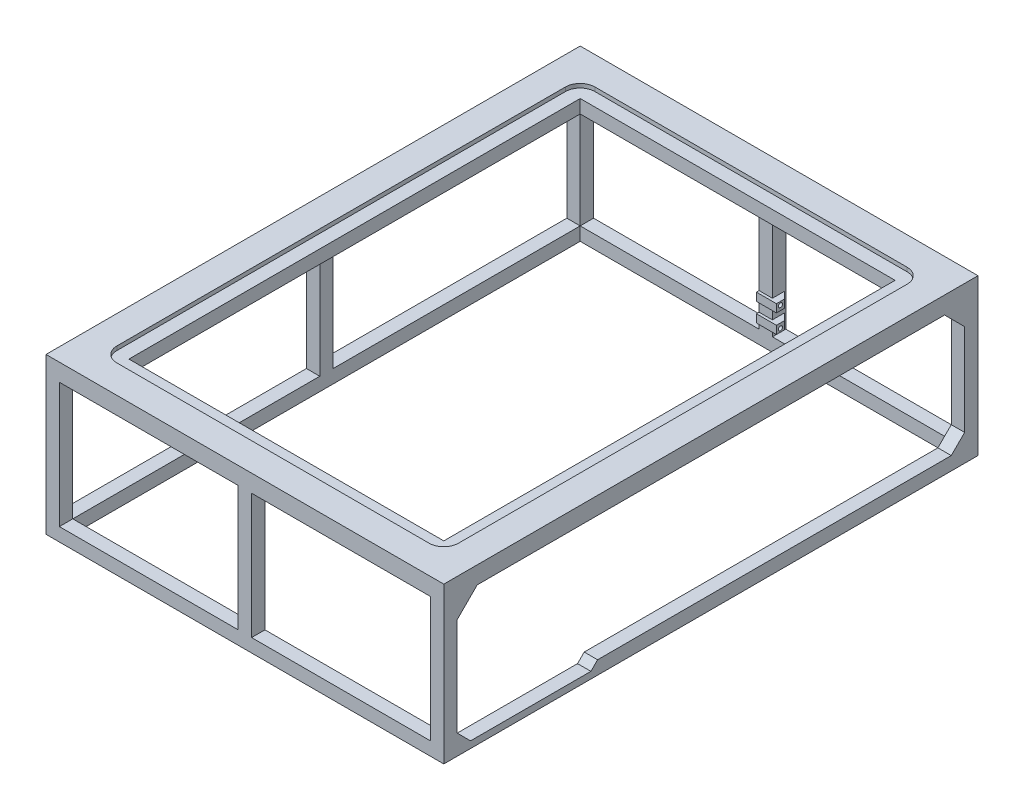
SolidWorks part; units mm, degrees
ref_plane "Front Plane" through (0, 0, 0) normal (0, 0, 1) x (1, 0, 0)
ref_plane "Top Plane" through (0, 0, 0) normal (0, 1, 0) x (1, 0, 0)
ref_plane "Right Plane" through (0, 0, 0) normal (1, 0, 0) x (0, 0, -1)
sketch "Sketch1" plane through (0, 0, 0) normal (0, 1, 0) x (1, 0, 0)
  line L1 (0, 0) -> (253.5, 0)
  line L2 (0, 0) -> (0, 355.5)
  line L3 (0, 355.5) -> (253.5, 355.5)
  line L4 (253.5, 0) -> (253.5, 355.5)
  line L5 (-22, 377.5) -> (275.5, 377.5)
  line L6 (-22, 377.5) -> (-22, -22)
  line L7 (-22, -22) -> (275.5, -22)
  line L8 (275.5, 377.5) -> (275.5, -22)
  line L9 (-12, 367.5) -> (265.5, 367.5)
  line L10 (-12, 367.5) -> (-12, -12)
  line L11 (-12, -12) -> (265.5, -12)
  line L12 (265.5, 367.5) -> (265.5, -12)
  dimension "D1" = 253.5
  dimension "D2" = 355.5
  dimension "D3" = 22
  dimension "D4" = 22
  dimension "D5" = 22
  dimension "D6" = 22
  dimension "D7" = 10
  dimension "D8" = 10
  dimension "D9" = 10
  dimension "D10" = 10
extrude "Boss-Extrude1" add sketch "Sketch1" along normal blind 10 contours L8 L5 L6 L7 L9 L12 L11 L10 region at (126.75, 0, -372.519)
sketch "Sketch2" plane through (0, 10, 0) normal (0, 1, 0) x (1, 0, 0)
  line L0 (-22, -22) -> (275.5, -22) construction
  line L1 (131.75, -22) -> (121.75, -22)
  line L2 (131.75, -22) -> (131.75, -12)
  line L3 (131.75, -12) -> (121.75, -12)
  line L4 (121.75, -22) -> (121.75, -12)
  line L5 (-12, -12) -> (265.5, -12) construction
  line L6 (-12, 367.5) -> (265.5, 367.5) construction
  line L7 (275.5, -22) -> (265.5, -22)
  line L8 (275.5, -22) -> (275.5, -12)
  line L9 (275.5, -12) -> (265.5, -12)
  line L10 (265.5, -22) -> (265.5, -12)
  line L11 (-22, -22) -> (-12, -22)
  line L12 (-22, -22) -> (-22, -12)
  line L13 (-22, -12) -> (-12, -12)
  line L14 (-12, -22) -> (-12, -12)
  line L15 (-22, 377.5) -> (-12, 377.5)
  line L16 (-22, 377.5) -> (-22, 367.5)
  line L17 (-22, 367.5) -> (-12, 367.5)
  line L18 (-12, 377.5) -> (-12, 367.5)
  line L19 (275.5, 377.5) -> (265.5, 377.5)
  line L20 (275.5, 377.5) -> (275.5, 367.5)
  line L21 (275.5, 367.5) -> (265.5, 367.5)
  line L22 (265.5, 377.5) -> (265.5, 367.5)
  line L23 (131.75, 367.5) -> (121.75, 367.5)
  line L24 (131.75, 367.5) -> (131.75, 377.5)
  line L25 (131.75, 377.5) -> (121.75, 377.5)
  line L26 (121.75, 367.5) -> (121.75, 377.5)
  line L27 (-22, 377.5) -> (275.5, 377.5) construction
  line L28 (275.5, 377.5) -> (275.5, -22) construction
  line L29 (275.5, 172.75) -> (265.5, 172.75)
  line L30 (275.5, 172.75) -> (275.5, 182.75)
  line L31 (275.5, 182.75) -> (265.5, 182.75)
  line L32 (265.5, 172.75) -> (265.5, 182.75)
  line L33 (265.5, 367.5) -> (265.5, -12) construction
  line L34 (-12, 367.5) -> (-12, -12) construction
  line L35 (-12, 172.75) -> (-22, 172.75)
  line L36 (-12, 172.75) -> (-12, 182.75)
  line L37 (-12, 182.75) -> (-22, 182.75)
  line L38 (-22, 172.75) -> (-22, 182.75)
  line L39 (-22, 377.5) -> (-22, -22) construction
  dimension "D1" = 133.75
  dimension "D2" = 10
  dimension "D3" = 133.75
  dimension "D4" = 10
  dimension "D5" = 133.75
  dimension "D6" = 10
  dimension "D7" = 184.75
  dimension "D8" = 184.75
  dimension "D9" = 10
  dimension "D10" = 184.75
extrude "Boss-Extrude2" add sketch "Sketch2" along normal blind 93.5
sketch "Sketch3" plane through (0, 103.5, 0) normal (0, 1, 0) x (1, 0, 0)
  line L1 (-22, 377.5) -> (275.5, 377.5)
  line L2 (-22, 377.5) -> (-22, -22)
  line L3 (-22, -22) -> (275.5, -22)
  line L4 (275.5, 377.5) -> (275.5, -22)
  line L9 (244.5, 346.5) -> (9, 346.5)
  line L10 (244.5, 346.5) -> (244.5, 9)
  line L11 (244.5, 9) -> (9, 9)
  line L12 (9, 346.5) -> (9, 9)
  dimension "D1" = 235.5
  dimension "D2" = 337.5
  dimension "D3" = 31
  dimension "D4" = 31
  dimension "D5" = 31
  dimension "D6" = 31
extrude "Boss-Extrude3" add sketch "Sketch3" along normal blind 10
sketch "Sketch4" plane through (0, 0, 0) normal (0, -1, 0) x (1, 0, 0)
  line L0 (-22, -177.75) -> (275.5, -177.75)
  line L1 (-22, -377.5) -> (-22, 22) construction
  line L2 (275.5, -377.5) -> (275.5, 22) construction
  line L3 (126.75, -377.5) -> (126.75, 22)
  line L4 (-22, -377.5) -> (275.5, -377.5) construction
  line L5 (-22, 22) -> (275.5, 22) construction
  line L6 (-17, -377.5) -> (-17, 22)
  line L7 (-22, -377.5) -> (275.5, -377.5)
  line L8 (-22, -377.5) -> (-22, -367.5)
  line L9 (-22, -367.5) -> (275.5, -367.5)
  line L10 (275.5, -377.5) -> (275.5, -367.5)
  line L11 (-22, 22) -> (275.5, 22)
  line L12 (-22, 22) -> (-22, 12)
  line L13 (-22, 12) -> (275.5, 12)
  line L14 (275.5, 22) -> (275.5, 12)
  line L15 (275.5, -377.5) -> (265.5, -377.5)
  line L16 (275.5, -377.5) -> (275.5, 22)
  line L17 (275.5, 22) -> (265.5, 22)
  line L18 (265.5, -377.5) -> (265.5, 22)
  line L19 (-22, -377.5) -> (-12, -377.5)
  line L20 (-22, -377.5) -> (-22, 22)
  line L21 (-22, 22) -> (-12, 22)
  line L22 (-12, -377.5) -> (-12, 22)
  line L23 (-22, 17) -> (275.5, 17)
  line L24 (-22, -372.5) -> (275.5, -372.5)
  line L25 (265.5, -367.5) -> (275.5, -377.5)
  line L26 (265.5, 12) -> (275.5, 22)
  line L27 (-22, -377.5) -> (-12, -367.5)
  line L28 (-12, 12) -> (-22, 22)
  circle A0 centre (270.5, 17) radius 1.6
  circle A1 centre (270.5, -177.75) radius 1.6
  circle A2 centre (270.5, -372.5) radius 1.6
  circle A3 centre (126.75, -372.5) radius 1.6
  circle A4 centre (-17, -372.5) radius 1.6
  circle A5 centre (-17, -177.75) radius 1.6
  circle A6 centre (-17, 17) radius 1.6
  circle A7 centre (126.75, 17) radius 1.6
  dimension "D1" = 3.2
  dimension "D2" = 3.2
  dimension "D3" = 3.2
  dimension "D4" = 3.2
  dimension "D5" = 3.2
  dimension "D6" = 3.2
  dimension "D7" = 3.2
  dimension "D8" = 3.2
extrude "Cut-Extrude1" cut sketch "Sketch4" against normal blind 1.2 contours L26 A0 L23 | L26 A0 L23 | L23 A0 L26 | L23 A0 L26 | L0 A1 | L0 A1 | L24 A2 L25 | L25 A2 L24 | L25 A2 L24 | L24 A2 L25 | L23 A7 L3 | L3 A7 L23 | L3 A7 L23 | L23 A7 L3 | L24 A3 L3 | L3 A3 L24 | L24 A3 L3 | L3 A3 L24 | L23 A6 L6 | L6 A6 L28 | L28 A6 L23 | L23 A6 L6 | L28 A6 L23 | L6 A6 L28 | L0 A5 L6 | L6 A5 L0 | L0 A5 L6 | L6 A5 L0 | L24 A4 L27 | L27 A4 L6 | L6 A4 L24 | L24 A4 L27 | L27 A4 L6 | L6 A4 L24 region at (270.5, 0, -178.4291) region at (270.5, 0, -177.0709) region at (270.8201, 0, -371.7272) region at (269.5397, 0, -372.1022) region at (271.4603, 0, -372.8978) region at (269.5397, 0, 16.6022) region at (270.8201, 0, 16.2272) region at (271.4603, 0, 17.3978) region at (127.4291, 0, -371.8209) region at (126.0709, 0, -371.8209) region at (127.4291, 0, -373.1791) region at (270.1799, 0, -373.2728) region at (126.0709, 0, 16.3209) region at (127.4291, 0, 16.3209) region at (127.4291, 0, 17.6791) region at (270.1799, 0, 17.7728) region at (-16.3209, 0, -178.4291) region at (-16.3209, 0, -177.0709) region at (126.0709, 0, -373.1791) region at (-16.0397, 0, -372.1022) region at (-16.6022, 0, -371.5397) region at (126.0709, 0, 17.6791) region at (-16.6022, 0, 16.0397) region at (-16.0397, 0, 16.6022) region at (-17.6791, 0, -178.4291) region at (-17.6791, 0, -177.0709) region at (-17.6791, 0, -371.8209) region at (-16.3209, 0, -373.1791) region at (-17.9603, 0, -372.8978) region at (-17.3978, 0, -373.4603) region at (-17.6791, 0, 16.3209) region at (-16.3209, 0, 17.6791) region at (-17.3978, 0, 17.9603) region at (-17.9603, 0, 17.3978)
sketch "Sketch6" plane through (0, 113.5, 0) normal (0, 1, 0) x (1, 0, 0)
  line L0 (253.5, 10) -> (253.5, 345.5) construction
  line L1 (10, 0) -> (243.5, 0) construction
  line L2 (0, 345.5) -> (0, 10) construction
  line L3 (243.5, 355.5) -> (10, 355.5) construction
  line L4 (253.5, 10) -> (253.5, 345.5)
  line L5 (10, 0) -> (243.5, 0)
  line L6 (0, 345.5) -> (0, 10)
  line L7 (243.5, 355.5) -> (10, 355.5)
  line L8 (254.5, 10) -> (254.5, 345.5)
  line L9 (243.5, 356.5) -> (10, 356.5)
  line L10 (-1, 345.5) -> (-1, 10)
  line L11 (10, -1) -> (243.5, -1)
  line L13 (275.5, 377.5) -> (-22, 377.5)
  line L14 (275.5, 377.5) -> (275.5, -22)
  line L15 (275.5, -22) -> (-22, -22)
  line L16 (-22, 377.5) -> (-22, -22)
  circle A0 centre (247.5, 349.5) radius 1.6 construction
  circle A1 centre (247.5, 263.625) radius 1.6 construction
  circle A2 centre (247.5, 177.75) radius 1.6 construction
  circle A3 centre (247.5, 91.875) radius 1.6 construction
  circle A4 centre (247.5, 6) radius 1.6 construction
  circle A5 centre (167, 6) radius 1.6 construction
  circle A6 centre (86.5, 6) radius 1.6 construction
  circle A7 centre (6, 6) radius 1.6 construction
  circle A8 centre (6, 91.875) radius 1.6 construction
  circle A9 centre (6, 177.75) radius 1.6 construction
  circle A10 centre (6, 263.625) radius 1.6 construction
  circle A11 centre (6, 349.5) radius 1.6 construction
  circle A12 centre (167, 349.5) radius 1.6 construction
  circle A13 centre (86.5, 349.5) radius 1.6 construction
  circle A14 centre (247.5, 349.5) radius 1.6
  circle A15 centre (247.5, 263.625) radius 1.6
  circle A16 centre (247.5, 177.75) radius 1.6
  circle A17 centre (247.5, 91.875) radius 1.6
  circle A18 centre (247.5, 6) radius 1.6
  circle A19 centre (167, 6) radius 1.6
  circle A20 centre (86.5, 6) radius 1.6
  circle A21 centre (6, 6) radius 1.6
  circle A22 centre (6, 91.875) radius 1.6
  circle A23 centre (6, 177.75) radius 1.6
  circle A24 centre (6, 263.625) radius 1.6
  circle A25 centre (6, 349.5) radius 1.6
  circle A26 centre (167, 349.5) radius 1.6
  circle A27 centre (86.5, 349.5) radius 1.6
  arc A28 (253.5, 345.5) -> (243.5, 355.5) centre (243.5, 345.5) ccw construction
  arc A29 (243.5, 0) -> (253.5, 10) centre (243.5, 10) ccw construction
  arc A30 (0, 10) -> (10, 0) centre (10, 10) ccw construction
  arc A31 (10, 355.5) -> (0, 345.5) centre (10, 345.5) ccw construction
  arc A32 (253.5, 345.5) -> (243.5, 355.5) centre (243.5, 345.5) ccw
  arc A33 (243.5, 0) -> (253.5, 10) centre (243.5, 10) ccw
  arc A34 (0, 10) -> (10, 0) centre (10, 10) ccw
  arc A35 (10, 355.5) -> (0, 345.5) centre (10, 345.5) ccw
  arc A36 (254.5, 345.5) -> (243.5, 356.5) centre (243.5, 345.5) ccw
  arc A37 (10, 356.5) -> (-1, 345.5) centre (10, 345.5) ccw
  arc A38 (-1, 10) -> (10, -1) centre (10, 10) ccw
  arc A39 (243.5, -1) -> (254.5, 10) centre (243.5, 10) ccw
  line M9 (-22, 377.5) -> (-22, -22)
  line M10 (-22, -22) -> (275.5, -22)
  line M11 (275.5, -22) -> (275.5, 377.5)
  line M12 (275.5, 377.5) -> (-22, 377.5)
  dimension "D1" = 1
extrude "Boss-Extrude4" add sketch "Sketch6" along normal up to surface (3 mm away) contours A39 L11 A38 L10 A37 L9 A36 L8 M12 M9 M10 M11 region at (270.519, 113.5, -177.75)
sketch "Sketch7" plane through (275.5, 0, 0) normal (1, 0, 0) x (0, 0, -1)
  line L0 (-12, 103.5) -> (172.75, 103.5) construction
  line L1 (170.75, 103.5) -> (184.75, 103.5)
  line L2 (170.75, 103.5) -> (170.75, 10)
  line L3 (170.75, 10) -> (184.75, 10)
  line L4 (184.75, 103.5) -> (184.75, 10)
  line L5 (367.5, 10) -> (182.75, 10) construction
  line L6 (172.75, 103.5) -> (172.75, 10) construction
  line L7 (182.75, 103.5) -> (182.75, 10) construction
  dimension "D1" = 2
  dimension "D2" = 2
extrude "Cut-Extrude2" cut sketch "Sketch7" against normal blind 16.15
chamfer "Chamfer1" distance 15 angle 45 2 edges at (270.5, 103.5, -367.5) (270.5, 103.5, 12)
sketch "Sketch8" plane through (131.75, 0, 0) normal (1, 0, 0) x (0, 0, -1)
  line L1 (371.5, 35) -> (365.5, 35)
  line L2 (371.5, 35) -> (371.5, 15)
  line L3 (371.5, 15) -> (365.5, 15)
  line L4 (365.5, 35) -> (365.5, 15)
  line L5 (369.5, 35) -> (353.5, 35) construction
  line L6 (371.5, 17) -> (371.5, 33) construction
  line L7 (353.5, 15) -> (369.5, 15) construction
  line L8 (367.5, 103.5) -> (367.5, 10) construction
  line L9 (371.5, 15) -> (365.5, 15)
  line L10 (371.5, 35) -> (365.5, 35)
  line L11 (371.5, 35) -> (371.5, 29)
  line L12 (371.5, 29) -> (365.5, 29)
  line L13 (365.5, 35) -> (365.5, 29)
  line L14 (371.5, 15) -> (371.5, 21)
  line L15 (371.5, 21) -> (365.5, 21)
  line L16 (365.5, 15) -> (365.5, 21)
  line M10 (367.5, 103.5) -> (367.5, 10)
  dimension "D1" = 0
  dimension "D2" = 0
  dimension "D3" = 0
  dimension "D4" = 2
  dimension "D5" = 6
  dimension "D6" = 6
extrude "Boss-Extrude5" add sketch "Sketch8" along normal blind 5 contours L12 L2 L1 M10 | L12 L1 L4 M10 | L2 L15 L3 M10 | L15 L4 L3 M10 region at (131.75, 32, -369.5) region at (131.75, 32, -366.5) region at (131.75, 18, -369.5) region at (131.75, 18, -366.5)
sketch "Sketch10" plane through (131.75, 0, 0) normal (-1, 0, 0) x (0, 0, 1)
  line L0 (-365.5, 21) -> (-367.5, 21) construction
  line L1 (-367.5, 21) -> (-367.5, 15) construction
  line L2 (-367.5, 15) -> (-365.5, 15) construction
  line L3 (-365.5, 15) -> (-365.5, 21) construction
  line L4 (-365.5, 35) -> (-367.5, 35) construction
  line L5 (-367.5, 35) -> (-367.5, 29) construction
  line L6 (-367.5, 29) -> (-365.5, 29) construction
  line L7 (-365.5, 29) -> (-365.5, 35) construction
  line L8 (-365.5, 21) -> (-367.5, 21)
  line L9 (-367.5, 21) -> (-367.5, 15)
  line L10 (-367.5, 15) -> (-365.5, 15)
  line L11 (-365.5, 15) -> (-365.5, 21)
  line L12 (-365.5, 35) -> (-367.5, 35)
  line L13 (-367.5, 35) -> (-367.5, 29)
  line L14 (-367.5, 29) -> (-365.5, 29)
  line L15 (-365.5, 29) -> (-365.5, 35)
extrude "Boss-Extrude6" add sketch "Sketch10" along normal up to surface (10 mm away) up to face at (121.75, 56.75, -372.5)
sketch "Sketch11" plane through (136.75, 0, 0) normal (1, 0, 0) x (0, 0, -1)
  arc A0 (370.05, 17.5) -> (366.95, 17.5) centre (368.5, 17.5) ccw construction
  arc A1 (366.95, 17.5) -> (370.05, 17.5) centre (368.5, 17.5) ccw construction
  arc A2 (370.05, 32.5) -> (366.95, 32.5) centre (368.5, 32.5) ccw construction
  arc A3 (366.95, 32.5) -> (370.05, 32.5) centre (368.5, 32.5) ccw construction
  arc A4 (370.05, 17.5) -> (366.95, 17.5) centre (368.5, 17.5) ccw
  arc A5 (366.95, 17.5) -> (370.05, 17.5) centre (368.5, 17.5) ccw
  arc A6 (370.05, 32.5) -> (366.95, 32.5) centre (368.5, 32.5) ccw
  arc A7 (366.95, 32.5) -> (370.05, 32.5) centre (368.5, 32.5) ccw
extrude "Cut-Extrude4" cut sketch "Sketch11" against normal blind 18
chamfer "Chamfer2" distance 5 angle 45 2 edges at (131.75, 18, -371.5) (131.75, 32, -371.5)
sketch "Sketch12" plane through (275.5, 0, 0) normal (1, 0, 0) x (0, 0, -1)
  line L0 (377.5, 0) -> (-22, 0) construction
  line L1 (-12, 10) -> (83, 10)
  line L2 (-12, 10) -> (-12, 5)
  line L3 (-12, 5) -> (83, 5)
  line L4 (83, 10) -> (83, 5)
  dimension "D1" = 95
  dimension "D2" = 5
extrude "Cut-Extrude5" cut sketch "Sketch12" against normal blind 10
chamfer "Chamfer3" distance 10 angle 45 3 edges at (270.5, 10, -367.5) (270.5, 5, 12) (270.5, 10, -83)
